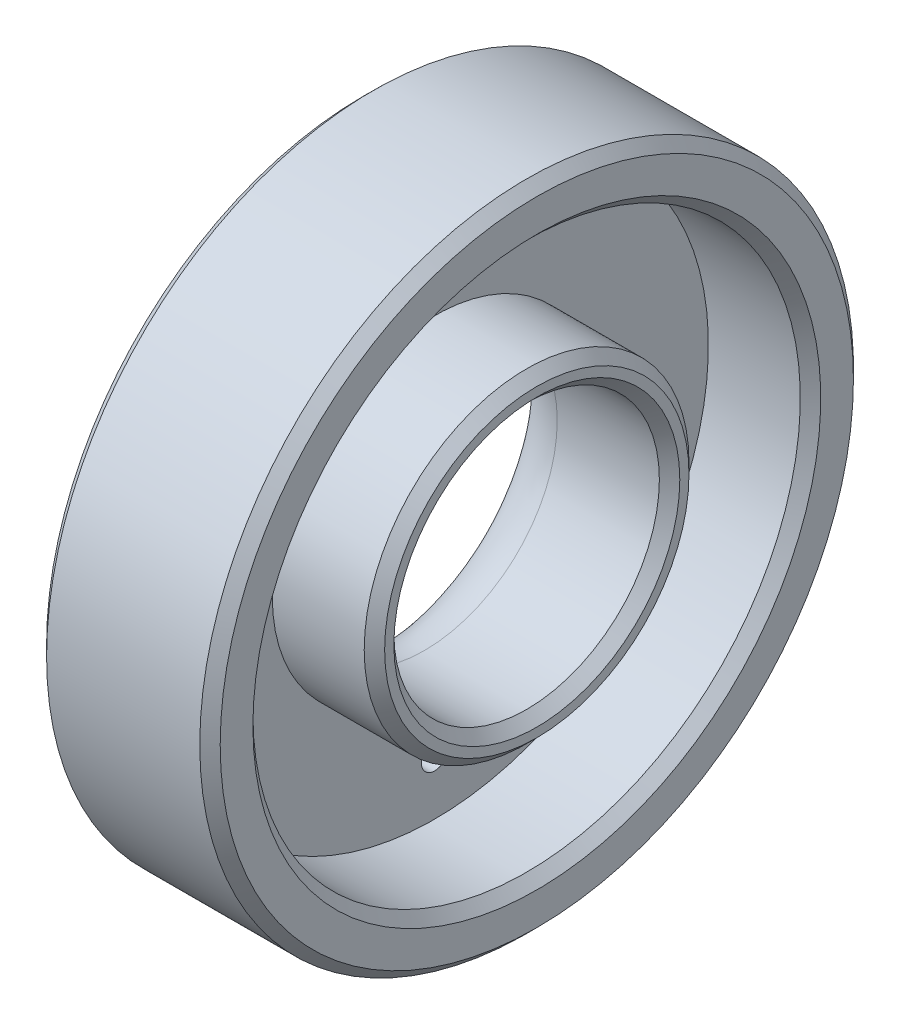
SolidWorks part; units mm, degrees
material "PVC hart"
ref_plane "Ebene vorne" through (0, 0, 0) normal (0, 0, 1) x (1, 0, 0)
ref_plane "Ebene oben" through (0, 0, 0) normal (0, 1, 0) x (1, 0, 0)
ref_plane "Ebene rechts" through (0, 0, 0) normal (1, 0, 0) x (0, 0, -1)
sketch "Skizze2" plane through (0, 0, 0) normal (0, 0, 1) x (1, 0, 0)
  line L0 (0, 0) -> (79.3276, 0) construction
  line L1 (0, 6.5) -> (0, 10)
  line L2 (0, 12.8) -> (0, 16)
  line L3 (0, 16) -> (8.5, 16)
  line L4 (8.5, 16) -> (8.5, 13.4)
  line L5 (8.5, 13.4) -> (3.5, 13.4)
  line L6 (3.5, 13.4) -> (3.5, 7.95)
  line L7 (3.5, 7.95) -> (8.5, 7.95)
  line L8 (8.5, 7.95) -> (8.5, 6.5)
  line L9 (8.5, 6.5) -> (0, 6.5)
  line L10 (0, 10) -> (1.2, 10)
  line L11 (1.2, 10) -> (1.2, 12.8)
  line L12 (1.2, 12.8) -> (0, 12.8)
  dimension "D5" = 20
  dimension "D1" = 13
  dimension "D2" = 15.9
  dimension "D3" = 26.8
  dimension "D4" = 1.2
  dimension "D6" = 32
  dimension "D7" = 5
  dimension "D8" = 5
  dimension "D9" = 3.5
  dimension "D10" = 25.6
revolve "Rotation1" add sketch "Skizze2" angle 360 about L0
chamfer "Fase1" distance 0.5 angle 45 5 edges at (0, 0, 16) (8.5, 0, 16) (8.5, 0, 13.4) (8.5, 0, 7.95) (8.5, 0, 6.5)
fillet "Verrundung1" radius 3 1 edges at (0, 0, 6.5)
hole_wizard "Ø1.3 (1.3) Durchmesser Bohrung1" positions "Skizze3" profile "Skizze4" hole size "Ø1.3" standard "DIN" end condition through all
sketch "Skizze3" plane through (1.2, 0, 0) normal (-1, 0, 0) x (0, 0, 1)
  line L0 (0, -55) -> (0, 55) construction
  line L1 (55, 0) -> (-55, 0) construction
  point P0 (0, 10.7)
  point P4 (0, -10.7)
  dimension "D1" = 10.7
  dimension "D2" = 21.4
sketch "Skizze4" plane through (1.2, 10.7, 0) normal (0, 1, 0) x (0, 0, 1)
  line L0 (0, 0) -> (0, 7.3)
  line L1 (0, 7.3) -> (0.65, 7.3)
  line L2 (0.65, 7.3) -> (0.65, 0)
  line L5 (0.65, 0) -> (0, 0)
  line L11 (0, -6.35) -> (0, 107.95) construction
  dimension "Bohrerdurchmesser" = 1.3
  dimension "Bohrungstiefe" = 7.3
fillet "Verrundung2" radius 0.2 2 edges at (1.2, 0, 12.8) (1.2, 0, 10)
equation "\"D2@Skizze3\"=\"D1@Skizze3\"*2"
